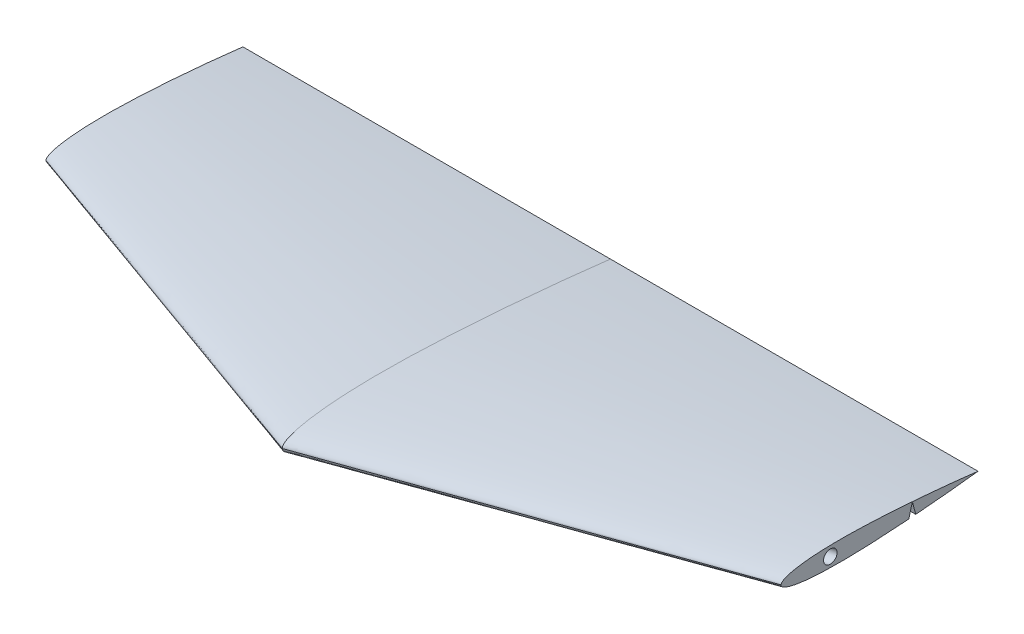
SolidWorks part; units mm, degrees
ref_plane "Front Plane" through (0, 0, 0) normal (0, 0, 1) x (1, 0, 0)
ref_plane "Top Plane" through (0, 0, 0) normal (0, 1, 0) x (1, 0, 0)
ref_plane "Right Plane" through (0, 0, 0) normal (1, 0, 0) x (0, 0, -1)
sketch "Sketch3" plane through (0, 0, 0) normal (1, 0, 0) x (0, 0, -1)
  line L0 (0, 0) -> (-250, 0) construction
  spline S0 degree 4 poles (-250, 0) (-249.9999, 0.1958) (-249.9612, 0.6039) (-249.7596, 1.2633) (-249.1282, 2.2398) (-248.1098, 3.1752) (-246.5761, 4.1828) (-244.1271, 5.3667) (-240.0739, 6.8179) (-232.84, 8.6113) (-221.2945, 10.4497) (-205.8077, 11.8178) (-187.4923, 12.5325) (-167.6157, 12.5624) (-147.9613, 12.1042) (-127.9831, 11.2209) (-108.5655, 10.1073) (-88.2725, 8.6479) (-69.4578, 7.1641) (-48.2492, 5.205) (-31.0441, 3.5474) (-5.6278, 0.7144) (5.3818, -0.6305) (19.3913, -2.4508) (24.9342, -3.2323) knots 0 0 0 0 0 0.002791 0.005883 0.009735 0.016522 0.022438 0.032158 0.048634 0.078249 0.129037 0.199997 0.270957 0.341918 0.412878 0.483838 0.554798 0.625759 0.696719 0.767679 0.83864 0.9096 1 1 1 1 1 construction
  spline S1 degree 4 poles (-250, 0) (-249.9999, 0.1958) (-249.9612, 0.6039) (-249.7596, 1.2633) (-249.1282, 2.2398) (-248.1098, 3.1752) (-246.5761, 4.1828) (-244.1271, 5.3667) (-240.0739, 6.8179) (-232.84, 8.6113) (-221.2945, 10.4497) (-205.8077, 11.8178) (-187.4923, 12.5325) (-167.6157, 12.5624) (-147.9613, 12.1042) (-127.9831, 11.2209) (-108.5655, 10.1073) (-88.2725, 8.6479) (-69.4578, 7.1641) (-48.2492, 5.205) (-31.0441, 3.5474) (-13.2038, 1.5588) (-4.4672, 0.5411) (0, 0) knots 0 0 0 0 0 0.002791 0.005883 0.009735 0.016522 0.022438 0.032158 0.048634 0.078249 0.129037 0.199997 0.270957 0.341918 0.412878 0.483838 0.554798 0.625759 0.696719 0.767679 0.83864 0.9096 0.9096 0.9096 0.9096 0.9096
  spline S2 degree 4 poles (-250, 0) (-249.9999, -0.1958) (-249.9612, -0.6039) (-249.7596, -1.2633) (-249.1282, -2.2398) (-248.1098, -3.1752) (-246.5761, -4.1828) (-244.1271, -5.3667) (-240.0739, -6.8179) (-232.84, -8.6113) (-221.2945, -10.4497) (-205.8077, -11.8178) (-187.4923, -12.5325) (-167.6157, -12.5624) (-147.9613, -12.1042) (-127.9831, -11.2209) (-108.5655, -10.1073) (-88.2725, -8.6479) (-69.4578, -7.1641) (-48.2492, -5.205) (-31.0441, -3.5474) (-13.2038, -1.5588) (-4.4672, -0.5411) (0, 0) knots 0 0 0 0 0 0.002791 0.005883 0.009735 0.016522 0.022438 0.032158 0.048634 0.078249 0.129037 0.199997 0.270957 0.341918 0.412878 0.483838 0.554798 0.625759 0.696719 0.767679 0.83864 0.9096 0.9096 0.9096 0.9096 0.9096
  dimension "D1" = 250
ref_plane "Plane1" through (280, 0, 0) normal (1, 0, 0) x (0, 0, -1)
sketch "Sketch4" plane through (280, 0, 0) normal (1, 0, 0) x (0, 0, -1)
  line L0 (0, 0) -> (-150, 0) construction
  spline S0 degree 4 poles (-150, 0) (-149.9999, 0.1175) (-149.9767, 0.3624) (-149.8557, 0.758) (-149.4769, 1.3439) (-148.8659, 1.9051) (-147.9457, 2.5097) (-146.4763, 3.22) (-144.0443, 4.0908) (-139.704, 5.1668) (-132.7767, 6.2698) (-123.4846, 7.0907) (-112.4954, 7.5195) (-100.5694, 7.5374) (-88.7768, 7.2625) (-76.7899, 6.7325) (-65.1393, 6.0644) (-52.9635, 5.1887) (-41.6747, 4.2985) (-28.9495, 3.123) (-18.6265, 2.1284) (-3.3767, 0.4286) (3.2291, -0.3783) (11.6348, -1.4705) (14.9605, -1.9394) knots 0 0 0 0 0 0.002791 0.005883 0.009735 0.016522 0.022438 0.032158 0.048634 0.078249 0.129037 0.199997 0.270957 0.341918 0.412878 0.483838 0.554798 0.625759 0.696719 0.767679 0.83864 0.9096 1 1 1 1 1 construction
  spline S1 degree 4 poles (-150, 0) (-149.9999, 0.1175) (-149.9767, 0.3624) (-149.8557, 0.758) (-149.4769, 1.3439) (-148.8659, 1.9051) (-147.9457, 2.5097) (-146.4763, 3.22) (-144.0443, 4.0908) (-139.704, 5.1668) (-132.7767, 6.2698) (-123.4846, 7.0907) (-112.4954, 7.5195) (-100.5694, 7.5374) (-88.7768, 7.2625) (-76.7899, 6.7325) (-65.1393, 6.0644) (-52.9635, 5.1887) (-41.6747, 4.2985) (-28.9495, 3.123) (-18.6265, 2.1284) (-7.9223, 0.9353) (-2.6803, 0.3247) (0, 0) knots 0 0 0 0 0 0.002791 0.005883 0.009735 0.016522 0.022438 0.032158 0.048634 0.078249 0.129037 0.199997 0.270957 0.341918 0.412878 0.483838 0.554798 0.625759 0.696719 0.767679 0.83864 0.9096 0.9096 0.9096 0.9096 0.9096
  spline S2 degree 4 poles (-150, 0) (-149.9999, -0.1175) (-149.9767, -0.3624) (-149.8557, -0.758) (-149.4769, -1.3439) (-148.8659, -1.9051) (-147.9457, -2.5097) (-146.4763, -3.22) (-144.0443, -4.0908) (-139.704, -5.1668) (-132.7767, -6.2698) (-123.4846, -7.0907) (-112.4954, -7.5195) (-100.5694, -7.5374) (-88.7768, -7.2625) (-76.7899, -6.7325) (-65.1393, -6.0644) (-52.9635, -5.1887) (-41.6747, -4.2985) (-28.9495, -3.123) (-18.6265, -2.1284) (-7.9223, -0.9353) (-2.6803, -0.3247) (0, 0) knots 0 0 0 0 0 0.002791 0.005883 0.009735 0.016522 0.022438 0.032158 0.048634 0.078249 0.129037 0.199997 0.270957 0.341918 0.412878 0.483838 0.554798 0.625759 0.696719 0.767679 0.83864 0.9096 0.9096 0.9096 0.9096 0.9096
loft "Loft1" add profiles "Sketch3", "Sketch4" connector at (0, 0, 0) connector at (280, 0, 0)
sketch "Sketch6" plane through (0, 0, 0) normal (-1, 0, 0) x (0, 0, 1)
  line L0 (0, 0) -> (249.9998, 0) construction
  line L1 (50, 0) -> (50, 5.2226) construction
  line L2 (50, 5.2226) -> (52.9065, -5.6245)
  line L3 (50, 5.2226) -> (47.2363, -5.0918)
  line L4 (52.9065, -5.6245) -> (53.3084, -7.1245)
  line L5 (53.3084, -7.1245) -> (46.6916, -7.1245)
  line L6 (46.6916, -7.1245) -> (47.2363, -5.0918)
  spline S1 degree 3 poles (249.9998, 0) (249.9998, -0.3303) (249.8759, -0.9899) (249.3864, -1.8624) (248.7238, -2.6034) (247.962, -3.2402) (247.1416, -3.797) (246.2828, -4.2923) (245.3979, -4.7388) (244.193, -5.2813) (242.6531, -5.88) (240.7719, -6.5042) (238.8684, -7.0564) (236.9492, -7.551) (235.0183, -7.9974) (233.0787, -8.4038) (231.1322, -8.7761) (229.1802, -9.1183) (227.2237, -9.4331) (225.2633, -9.7232) (223.2997, -9.9908) (220.6781, -10.3206) (217.3955, -10.6866) (213.4499, -11.0625) (209.4994, -11.3825) (205.5452, -11.6532) (201.5883, -11.8796) (197.6292, -12.0662) (193.6687, -12.2161) (188.3864, -12.3703) (181.7816, -12.4844) (173.8547, -12.5144) (165.9281, -12.4534) (158.0025, -12.3124) (150.0786, -12.0979) (142.1568, -11.8164) (134.2373, -11.4769) (126.32, -11.0887) (118.4051, -10.6559) (110.4927, -10.178) (102.5832, -9.6561) (94.6761, -9.0972) (86.7712, -8.5097) (78.8683, -7.8944) (70.9683, -7.2438) (63.0715, -6.5557) (55.1773, -5.8381) (47.285, -5.1002) (39.3948, -4.3397) (31.5085, -3.54) (23.6262, -2.7007) (13.1211, -1.5408) (5.2462, -0.6354) (0, 0) knots 0.499997 0.499997 0.499997 0.499997 0.50195 0.503903 0.505856 0.507809 0.509763 0.511716 0.513669 0.515622 0.519528 0.523435 0.527341 0.531247 0.535153 0.53906 0.542966 0.546872 0.550778 0.554685 0.558591 0.562497 0.57031 0.578122 0.585935 0.593748 0.60156 0.609373 0.617185 0.624998 0.640623 0.656248 0.671873 0.687498 0.703123 0.718748 0.734373 0.749998 0.765624 0.781249 0.796874 0.812499 0.828124 0.843749 0.859374 0.874999 0.890624 0.906249 0.921875 0.9375 0.953125 0.96875 1 1 1 1 construction
  point P6 (0, 0)
  point P8 (0, 0)
  point P13 (75, 7.3485)
  point P14 (50, 5.2226)
  dimension "D1" = 50
  dimension "D2" = 15
  dimension "D3" = 15
  dimension "D4" = 1.5
sketch "Sketch7" plane through (280, 0, 0) normal (1, 0, 0) x (0, 0, -1)
  line L0 (-149.9999, 0) -> (0, 0) construction
  line L1 (-50, 0) -> (-50, 4.8685) construction
  line L2 (-50, 4.8685) -> (-47.425, -4.7416)
  line L3 (-50, 4.8685) -> (-52.6846, -5.1507)
  line L4 (-52.6846, -5.1507) -> (-53.0866, -6.6507)
  line L5 (-53.0866, -6.6507) -> (-46.9134, -6.6507)
  line L6 (-46.9134, -6.6507) -> (-47.425, -4.7416)
  spline S1 degree 2 poles (-149.9999, 0) (-149.9999, -1.0092) (-148.7713, -1.9362) (-147.9824, -2.5314) (-146.6951, -3.0843) (-144.8841, -3.862) (-142.1683, -4.5258) (-138.2655, -5.4797) (-132.7998, -6.141) (-128.4814, -6.6636) (-123.3268, -6.9875) (-118.8418, -7.2693) (-113.824, -7.3959) (-105.2058, -7.6134) (-94.8016, -7.3801) (-86.1557, -7.1862) (-75.7922, -6.6487) (-71.0007, -6.4001) (-66.2959, -6.1026) (-61.9956, -5.8307) (-56.8059, -5.4552) (-51.7767, -5.0913) (-47.3212, -4.7333) (-42.7854, -4.3688) (-37.8431, -3.9303) (-33.2978, -3.527) (-28.3712, -3.0577) (-23.1272, -2.5583) (-18.9054, -2.1204) (-14.7262, -1.687) (-9.4487, -1.0957) (-4.0863, -0.4949) (0, 0) knots 0 0 0 0.015625 0.015625 0.03125 0.03125 0.0625 0.0625 0.125 0.125 0.1875 0.1875 0.25 0.25 0.375 0.375 0.5 0.5 0.5625 0.5625 0.625 0.625 0.6875 0.6875 0.75 0.75 0.8125 0.8125 0.875 0.875 0.9375 0.9375 1 1 1 construction
  point P6 (-75, 6.5393)
  point P7 (-50, 4.5956)
  point P8 (0, 0)
  point P15 (-50, 4.7972)
  point P16 (-50, 4.8685)
  dimension "D1" = 50
  dimension "D2" = 15
  dimension "D3" = 15
  dimension "D4" = 1.5
loft "Cut-Loft1" cut profiles "Sketch6", "Sketch7" connector at (0, -5.0918, 47.2363) connector at (280, -4.7416, 47.425)
sketch "Sketch8" plane through (0, 0, 0) normal (-1, 0, 0) x (0, 0, 1)
  line L0 (0, 0) -> (249.9998, 0) construction
  point P4 (187.4998, 0)
  dimension "D1" = 62.5
sketch "Sketch9" plane through (280, 0, 0) normal (1, 0, 0) x (0, 0, -1)
  line L0 (-149.9999, 0) -> (0, 0) construction
  point P4 (-112.4999, 0)
  dimension "D1" = 37.5
ref_axis "Axis1" through (0, 0, 187.4998) along (0.9659, 0, -0.2587)
ref_plane "Plane3" through (280, 0, 112.4999) normal (-0.9659, 0, 0.2587) x (0.2587, 0, 0.9659)
sketch "Sketch10" plane through (280, 0, 112.4999) normal (-0.9659, 0, 0.2587) x (0.2587, 0, 0.9659)
  circle A0 centre (0, 0) radius 5
  dimension "D1" = 10
extrude "Cut-Extrude1" cut sketch "Sketch10" against normal up to surface and the other way up to surface up to face at (280, -0.923, 58.97) other way up to face at (0, -1.0987, 80.0285)
mirror "Mirror1" about plane through (0, -11.0805, 126.3057) normal (-1, 0, 0) of "Cut-Extrude1", "Loft1", "Cut-Loft1"
